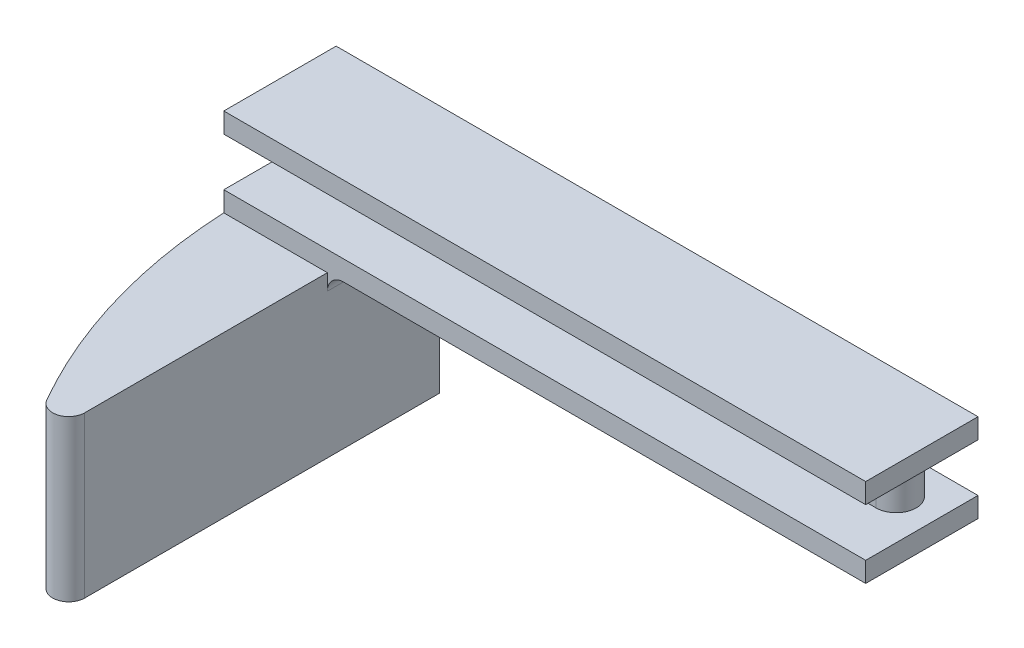
SolidWorks part; units mm, degrees
ref_plane "Front Plane" through (0, 0, 0) normal (0, 0, 1) x (1, 0, 0)
ref_plane "Top Plane" through (0, 0, 0) normal (0, 1, 0) x (1, 0, 0)
ref_plane "Right Plane" through (0, 0, 0) normal (1, 0, 0) x (0, 0, -1)
sketch "Sketch2" plane through (0, 0, 0) normal (0, 1, 0) x (1, 0, 0)
  line L1 (0, 0) -> (101.6, 0)
  line L2 (0, 0) -> (0, 17.78)
  line L3 (0, 17.78) -> (101.6, 17.78)
  line L4 (101.6, 0) -> (101.6, 17.78)
  dimension "D1" = 17.78
  dimension "D2" = 101.6
extrude "Boss-Extrude1" add sketch "Sketch2" along normal blind 3.175
sketch "Sketch3" plane through (0, 0, 0) normal (0, -1, 0) x (1, 0, 0)
  line L0 (95.25, -11.176) -> (6.35, -11.176) construction
  line L1 (95.25, -14.351) -> (6.35, -14.351)
  line L2 (95.25, -8.001) -> (6.35, -8.001)
  line L3 (0, 0) -> (101.6, 0) construction
  line L4 (0, -17.78) -> (0, 0) construction
  arc A0 (95.25, -14.351) -> (95.25, -8.001) centre (95.25, -11.176) ccw
  arc A1 (6.35, -8.001) -> (6.35, -14.351) centre (6.35, -11.176) ccw
  point P2 (50.8, -11.176)
  dimension "D1" = 88.9
  dimension "D2" = 11.176
  dimension "D3" = 6.35
  dimension "D4" = 6.35
extrude "Boss-Extrude2" add sketch "Sketch3" along normal blind 7.62 contours L2 A1 L1 A0
ref_plane "Plane1" through (0, -3.81, 0) normal (0, -1, 0) x (-1, 0, 0)
mirror "Mirror1" about plane through (0, -3.81, 0) normal (0, -1, 0) of "Boss-Extrude1"
sketch "Sketch4" plane through (0, -10.795, 0) normal (0, -1, 0) x (1, 0, 0)
  line L0 (0, 0) -> (101.6, 0) construction
  line L1 (0, -17.78) -> (16.3938, -17.78)
  line L2 (0, -17.78) -> (0, 0)
  line L4 (16.3938, -17.78) -> (16.3938, 0)
  line L5 (16.3938, 0) -> (16.3938, 47.009)
  arc A0 (0, 0) -> (16.3938, 47.009) centre (87.5, -4.1516) cw
extrude "Boss-Extrude3" add sketch "Sketch4" along normal blind 25.4
fillet "Fillet1" radius 2.54 1 edges at (16.3938, -10.795, -8.89)
fillet "Fillet2" radius 2.54 1 edges at (16.3938, -23.495, 47.009)
